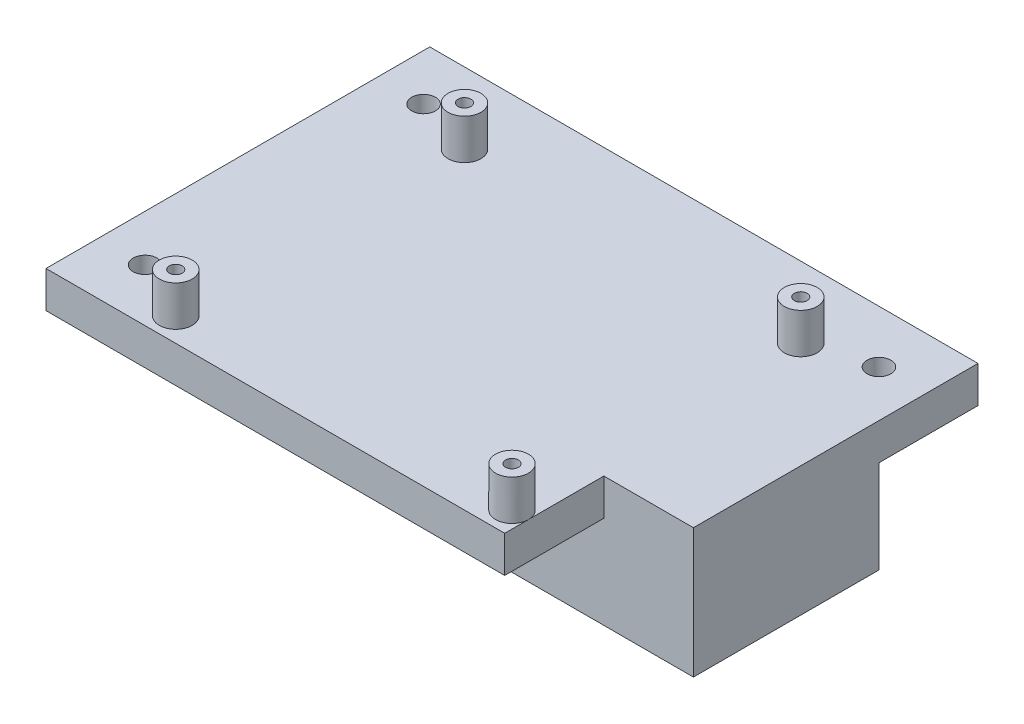
SolidWorks part; units mm, degrees
material "PETG"
ref_plane "Front Plane" through (0, 0, 0) normal (0, 0, 1) x (1, 0, 0)
ref_plane "Top Plane" through (0, 0, 0) normal (0, 1, 0) x (1, 0, 0)
ref_plane "Right Plane" through (0, 0, 0) normal (1, 0, 0) x (0, 0, -1)
sketch "Sketch1" plane through (0, 0, 0) normal (0, 1, 0) x (1, 0, 0)
  line L0 (-62.3, 38.1) -> (-75, 38.1) construction
  line L1 (-75, -25.3625) -> (75, -25.3625)
  line L2 (-75, -25.3625) -> (-75, 25.3625)
  line L3 (-75, 25.3625) -> (75, 25.3625)
  line L4 (75, -25.3625) -> (75, 25.3625)
  line L5 (-75, 52.5) -> (75, 52.5)
  line L6 (-75, 52.5) -> (-75, -52.5)
  line L7 (-75, -52.5) -> (75, -52.5)
  line L8 (75, 52.5) -> (75, -52.5)
  line L11 (62.3, 38.1) -> (75, 38.1) construction
  circle A0 centre (-62.3, 38.1) radius 3.25
  circle A1 centre (62.3, 38.1) radius 3.25
  circle A2 centre (-62.3, -38.1) radius 3.25
  circle A3 centre (62.3, -38.1) radius 3.25
  point P4 (-75, 0)
  point P5 (0, 25.3625)
  dimension "D4" = 6.5
  dimension "D1" = 50.725
  dimension "D2" = 150
  dimension "D3" = 105
  dimension "D5" = 38.1
  dimension "D6" = 12.7
  dimension "D7" = 38.1
extrude "Boss-Extrude1" add sketch "Sketch1" along normal blind 10 contours L1 L4 L3 L2 | L8 L1 L6 L7 | L8 L5 L6 L3 region at (0, 0, 0) region at (0, 0, 38.945) region at (0, 0, -38.945)
extrude "Boss-Extrude2" add sketch "Sketch1<3>" against normal blind 25.4 contours L1 L4 L3 L2 region at (0, 0, 0)
sketch "Sketch1<3>" plane through (0, 0, 0) normal (0, 1, 0) x (1, 0, 0) same geometry as "Sketch1"
sketch "Sketch2" plane through (0, 10, 0) normal (0, 1, 0) x (1, 0, 0)
  line L0 (-46, 33) -> (-46, -46) construction
  line L1 (-46, -46) -> (46, -46) construction
  line L2 (46, -46) -> (46, 33) construction
  line L3 (46, 33) -> (-46, 33) construction
  line L4 (-75, -52.5) -> (75, -52.5) construction
  line L6 (-75, 52.5) -> (75, 52.5) construction
  line L8 (-46, 0) -> (46, 0) construction
  circle A0 centre (-46, 33) radius 4.5
  circle A1 centre (-46, 33) radius 1.75
  circle A2 centre (46, 33) radius 4.5
  circle A3 centre (46, 33) radius 1.75
  circle A4 centre (46, -46) radius 4.5
  circle A5 centre (46, -46) radius 1.75
  circle A6 centre (-46, -46) radius 4.5
  circle A7 centre (-46, -46) radius 1.75
  point P19 (0, 0)
  dimension "D1" = 3.5
  dimension "D2" = 9
  dimension "D3" = 6.5
  dimension "D4" = 92
  dimension "D5" = 19.5
extrude "Boss-Extrude3" add sketch "Sketch2" along normal blind 11
extrude "Cut-Extrude4" cut sketch "Sketch2<3>" against normal up to next contours A1 | A3 | A5 | A7 region at (-46, 10, -33)
sketch "Sketch2<3>" plane through (0, 10, 0) normal (0, 1, 0) x (1, 0, 0) same geometry as "Sketch2"
sketch "Sketch3" plane through (0, 10, 0) normal (0, 1, 0) x (1, 0, 0)
  circle A0 centre (-46, 33) radius 3.2
  circle A1 centre (46, 33) radius 3.2
  circle A2 centre (46, -46) radius 3.2
  circle A3 centre (-46, -46) radius 3.2
  dimension "D1" = 6.4
extrude "Cut-Extrude3" cut sketch "Sketch3" against normal up to next from offset 3.5 offset against normal yes
sketch "Sketch4" plane through (0, 10, 0) normal (0, 1, 0) x (1, 0, 0)
  line L0 (-75, -25.3625) -> (75, -25.3625) construction
  line L1 (75, -52.5) -> (50.5, -52.5)
  line L2 (75, -52.5) -> (75, -25.3625)
  line L3 (75, -25.3625) -> (50.5, -25.3625)
  line L4 (50.5, -52.5) -> (50.5, -25.3625)
  circle A0 centre (46, -46) radius 4.5 construction
extrude "Cut-Extrude5" cut sketch "Sketch4" against normal up to vertex (10 mm away) up to point (75, 0, 25.3625)
equation "\"tol_dia_id_intfc\" = 0.0500mm ' For hole diameters - Interference fit"
equation "\"tol_dia_id_slip\"  = 0.0750mm ' For hole diameters - Slip fit"
equation "\"tol_dia_id_clear\" = 0.1000mm ' For hole diameters - Clearance fit"
equation "\"tol_dia_od_intfc\" = 0.0500mm ' For shaft diameters - Interference fit"
equation "\"tol_dia_od_slip\"  = 0.0750mm ' For shaft diameters - Slip fit"
equation "\"tol_dia_od_clear\" = 0.1000mm ' For shaft diameters - Clearance fit"
equation "\"tol_general_intfc\"= 0.0250mm ' For general parts (Horiz) - Interference fit"
equation "\"tol_general_slip\" = 0.0375mm ' For general parts (Horiz) - Slip fit"
equation "\"tol_general_clear\"= 0.0500mm ' For general parts (Horiz) - Clearance fit"
equation "\"tol_layer_intfc\"  = 0.0250mm ' For all parts (Vert) - Interference fit"
equation "\"tol_layer_slip\"   = 0.0375mm ' For all parts (Vert) - Slip fit"
equation "\"tol_layer_clear\"  = 0.0500mm ' For all parts (Vert) - Clearance fit"
equation "\"tol_corner_rad\"   = 0.100mm ' For corners that fit into other parts"
equation "\"D1@Sketch1\"=50.80mm-\"tol_general_slip\"*2"
